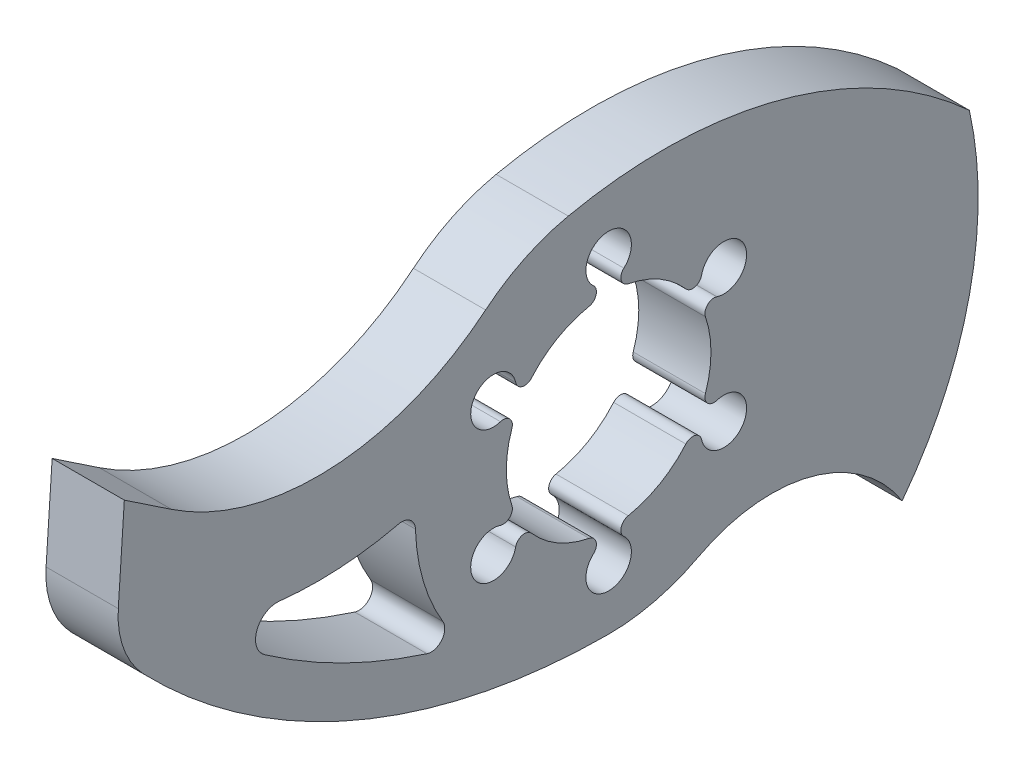
SolidWorks part; units mm, degrees
material "1023 Carbon Steel Sheet (SS)"
ref_plane "Front Plane" through (0, 0, 0) normal (0, 0, 1) x (1, 0, 0)
ref_plane "Top Plane" through (0, 0, 0) normal (0, 1, 0) x (1, 0, 0)
ref_plane "Right Plane" through (0, 0, 0) normal (1, 0, 0) x (0, 0, -1)
other "Center of Mass"
ref_plane "Plane1" through (6.35, 0, 0) normal (1, 0, 0) x (0, 0, -1)
sketch "Sketch1" plane through (0, 0, 0) normal (1, 0, 0) x (0, 0, -1)
  line L0 (-45, 0) -> (45, 0) construction
  line L1 (0, 11.7) -> (-10.1325, 5.85)
  line L2 (-10.1325, 5.85) -> (-10.1325, -5.85)
  line L3 (-10.1325, -5.85) -> (0, -11.7)
  line L4 (0, -11.7) -> (10.1325, -5.85)
  line L5 (10.1325, -5.85) -> (10.1325, 5.85)
  line L6 (10.1325, 5.85) -> (0, 11.7)
  line L7 (0, 45) -> (0, -45) construction
  circle A0 centre (0, 0) radius 45
  circle A1 centre (0, 0) radius 10.1325 construction
  circle A2 centre (0, 0) radius 17
  circle A3 centre (0, 0) radius 32.5
  circle A4 centre (0, 0) radius 9
  dimension "D1" = 90
  dimension "D3" = 34
  dimension "D4" = 65
  dimension "D5" = 18
  dimension "D2" = 23.4
sketch "Sketch2" plane through (0, 0, 0) normal (1, 0, 0) x (0, 0, -1)
  line L0 (-42.5954, 14.513) -> (-43.1289, 6.513)
  line L1 (-42.5954, 14.513) -> (0, 0) construction
  line L2 (-45, 0) -> (45, 0) construction
  line L3 (-42.5954, 14.513) -> (-38.4412, 11.7305)
  line L4 (31.7283, 7.0403) -> (21.8458, 16.0801) construction
  line L5 (25.8147, -19.7446) -> (20.7849, -11.8646) construction
  line L6 (-23.3781, -7.5057) -> (-25.1515, -11.0911) construction
  line L7 (-23.6822, -0.129) -> (-24.164, 7.8565) construction
  line L8 (31.7283, 7.0403) -> (25.8147, -19.7446) construction
  line L9 (0, 0) -> (28.7715, -6.3522) construction
  line L11 (-3.5483, 16.6256) -> (0, 0) construction
  circle A0 centre (0, 0) radius 45 construction
  arc A1 (-43.1289, 6.513) -> (-40.9039, 0.4262) centre (-35.1466, 5.9808) ccw
  arc A2 (-0.0524, -16.9999) -> (7.9477, -15.0278) centre (0, 0) ccw
  circle A3 centre (0, 0) radius 17 construction
  arc A4 (-10.8217, 13.1107) -> (-3.5483, 16.6256) centre (0, 0) cw
  arc A5 (-10.8217, 13.1107) -> (-38.4412, 11.7305) centre (-25.5582, 30.9642) cw
  arc A6 (-40.9039, 0.4262) -> (-0.0524, -16.9999) centre (0.1234, 40.0089) ccw
  arc A7 (7.9477, -15.0278) -> (25.8147, -19.7446) centre (14.3219, -27.0804) cw
  circle A8 centre (0, 0) radius 32.5 construction
  arc A9 (-3.5483, 16.6256) -> (31.7283, 7.0403) centre (4.7841, -22.4157) cw
  arc A10 (-16.9926, -0.5004) -> (-14.5838, -8.7358) centre (0, 0) ccw
  arc A11 (31.7283, 7.0403) -> (25.8147, -19.7446) centre (0, 0) cw
  arc A12 (-16.9926, -0.5004) -> (-18.4654, 0.6327) centre (-18.1921, -0.5357) ccw
  arc A13 (-14.5838, -8.7358) -> (-15.9777, -10.4957) centre (-15.6132, -9.3524) cw
  arc A14 (-15.9777, -10.4957) -> (-30.2457, -3.4385) centre (0.1234, 40.0089) cw
  arc A15 (-18.4654, 0.6327) -> (-28.9529, 0) centre (-25.5582, 30.9642) cw
  arc A16 (-28.9529, 0) -> (-30.2457, -3.4385) centre (-29.1595, -1.8846) ccw
  circle A17 centre (0, 0) radius 9
  circle A18 centre (0, 0) radius 9 construction
  dimension "D5" = 8
  dimension "D6" = 1.2
  dimension "D1" = 15
  dimension "D2" = 5
  dimension "D3" = 75
  dimension "D4" = 8
  dimension "D7" = 4
  dimension "D8" = 8
  dimension "D9" = 27.43
  dimension "D10" = 12.45
  dimension "D11" = 45
  dimension "D12" = 30
extrude "Boss-Extrude1" add sketch "Sketch2" along normal up to surface (6.35 mm away) up to plane "Plane1"
ref_axis "Axis1" through (0, 0, 0) along (1, 0, 0)
sketch "Sketch3" plane through (6.35, 0, 0) normal (1, 0, 0) x (0, 0, -1)
  circle A0 centre (0, 11.7) radius 2
  circle A1 centre (10.1325, 5.85) radius 2
  circle A2 centre (10.1325, -5.85) radius 2
  circle A3 centre (0, -11.7) radius 2
  circle A4 centre (-10.1325, -5.85) radius 2
  circle A5 centre (-10.1325, 5.85) radius 2
  dimension "D1" = 4
extrude "Cut-Extrude1" cut sketch "Sketch3" against normal through all
sketch "Sketch5" plane through (6.35, 0, 0) normal (1, 0, 0) x (0, 0, -1)
  line L0 (0, 11.7) -> (0, 0) construction
  arc A0 (-1.3383, 10.2137) -> (1.3383, 10.2137) centre (0, 11.7) ccw
  circle A1 centre (0, 11.7) radius 2 construction
  arc A2 (-1.3383, 10.2137) -> (-1.7207, 8.834) centre (-1.8736, 9.6192) cw
  arc A3 (-1.7207, 8.834) -> (1.7207, 8.834) centre (0, 0) cw
  circle A4 centre (0, 0) radius 9 construction
  arc A5 (1.3383, 10.2137) -> (1.7207, 8.834) centre (1.8736, 9.6192) ccw
  dimension "D1" = 0.8
extrude "Cut-Extrude2" cut sketch "Sketch5" against normal through all contours A3 A5 A0 A2
pattern_circular "CirPattern1" count 6 over 360 about axis through (0, 0, 0) along (1, 0, 0) of "Cut-Extrude2"
sketch "Sketch6" plane through (0, 0, 0) normal (1, 0, 0) x (0, 0, -1)
  circle A0 centre (0, 0) radius 29.2203 construction
  circle A1 centre (-29.1595, -1.8846) radius 1.8959 construction
sketch "Sketch4" plane through (0, 0, 0) normal (-1, 0, 0) x (0, 0, 1)
  circle A0 centre (0, 0) radius 17 construction
  circle A1 centre (0, 0) radius 17
  circle A2 centre (0, 0) radius 45 construction
  circle A3 centre (0, 0) radius 45
extrude "Boss-Extrude2" [suppressed] add sketch "Sketch4" against normal up to surface (6.35 mm away) up to face at (6.35, 0, 0)
